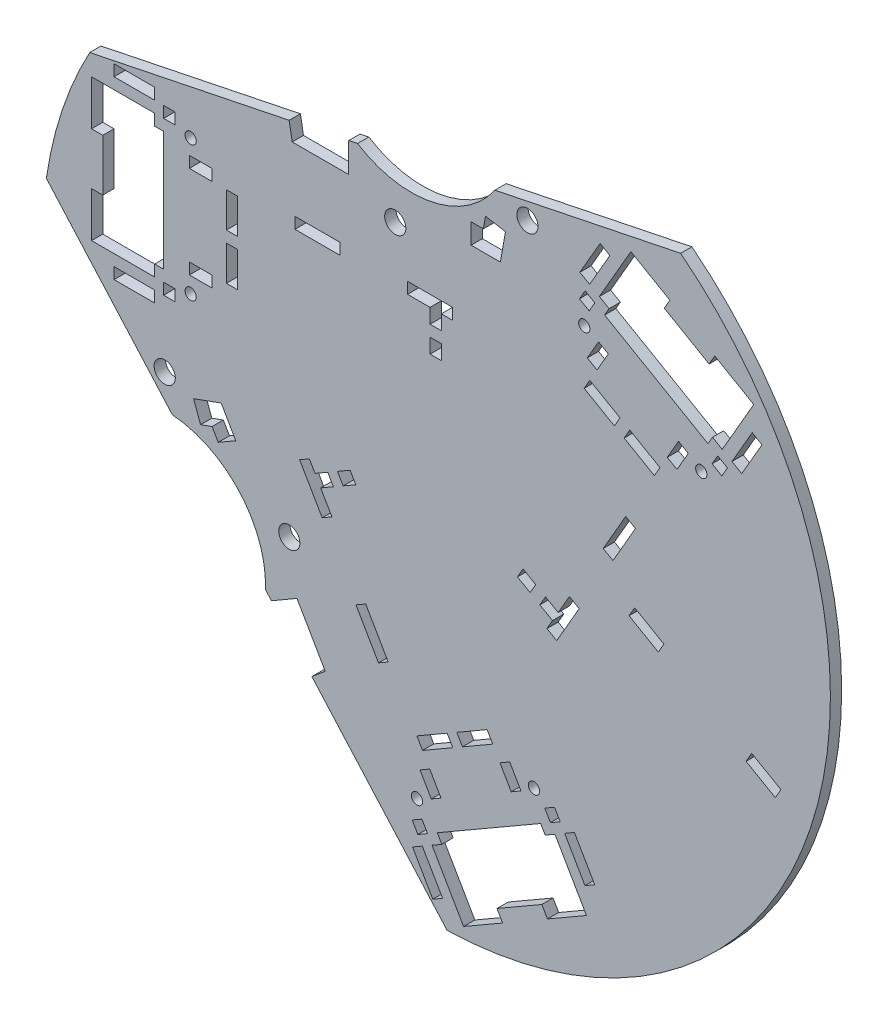
SolidWorks part; units mm, degrees
material "Balsa"
ref_plane "Plan de face" through (0, 0, 0) normal (0, 0, 1) x (1, 0, 0)
ref_plane "Plan de dessus" through (0, 0, 0) normal (0, 1, 0) x (1, 0, 0)
ref_plane "Plan de droite" through (0, 0, 0) normal (1, 0, 0) x (0, 0, -1)
sketch "Esquisse1" plane through (0, 0, 0) normal (0, 0, 1) x (1, 0, 0)
  circle A0 centre (148.0804, -12.1102) radius 175
extrude "Boss.-Extru.1" add sketch "Esquisse1" along normal blind 5
sketch "Esquisse2" plane through (0, 0, 0) normal (0, 0, -1) x (-1, 0, 0)
  line L0 (-155.3118, 53.7774) -> (-135.3118, 53.7774)
  line L1 (-150.3118, 37.2774) -> (-145.3118, 37.2774)
  line L2 (-150.3118, 37.2774) -> (-150.3118, 30.7774)
  line L3 (-150.3118, 30.7774) -> (-145.3118, 30.7774)
  line L4 (-145.3118, 37.2774) -> (-145.3118, 30.7774)
  line L5 (-105.3118, 53.7774) -> (-85.3118, 53.7774)
  line L6 (-105.3118, 53.7774) -> (-105.3118, 48.7774)
  line L7 (-105.3118, 48.7774) -> (-85.3118, 48.7774)
  line L8 (-85.3118, 53.7774) -> (-85.3118, 48.7774)
  line L9 (-59.86, 48.7774) -> (-54.86, 48.7774)
  line L10 (-59.86, 48.7774) -> (-59.86, 33.2774)
  line L11 (-59.86, 33.2774) -> (-54.86, 33.2774)
  line L12 (-54.86, 48.7774) -> (-54.86, 33.2774)
  line L13 (-59.86, 28.2774) -> (-54.86, 28.2774)
  line L14 (-59.86, 28.2774) -> (-59.86, 12.7774)
  line L15 (-59.86, 12.7774) -> (-54.86, 12.7774)
  line L16 (-54.86, 28.2774) -> (-54.86, 12.7774)
  line L17 (-48.43, 12.7774) -> (-38.43, 12.7774)
  line L18 (-48.43, 12.7774) -> (-48.43, 7.7774)
  line L19 (-48.43, 7.7774) -> (-38.43, 7.7774)
  line L20 (-38.43, 12.7774) -> (-38.43, 7.7774)
  line L21 (-32, -0.7226) -> (-27, -0.7226)
  line L22 (-32, -0.7226) -> (-32, -5.7226)
  line L23 (-32, -5.7226) -> (-27, -5.7226)
  line L24 (-27, -0.7226) -> (-27, -5.7226)
  line L25 (-23, -5.7226) -> (-5, -5.7226)
  line L26 (-23, -5.7226) -> (-23, -10.7226)
  line L27 (-23, -10.7226) -> (-5, -10.7226)
  line L28 (-5, -5.7226) -> (-5, -10.7226)
  line L29 (0, -0.7226) -> (5, -0.7226)
  line L30 (0, -0.7226) -> (0, 19.2774)
  line L31 (0, 19.2774) -> (5, 19.2774)
  line L32 (5, -0.7226) -> (5, 19.2774)
  line L33 (0, 42.2774) -> (5, 42.2774)
  line L34 (0, 42.2774) -> (0, 62.2774)
  line L35 (0, 62.2774) -> (5, 62.2774)
  line L36 (5, 42.2774) -> (5, 62.2774)
  line L37 (-23, 67.2774) -> (-5, 67.2774)
  line L38 (-23, 67.2774) -> (-23, 72.2774)
  line L39 (-23, 72.2774) -> (-5, 72.2774)
  line L40 (-5, 67.2774) -> (-5, 72.2774)
  line L41 (-27, 67.2774) -> (-32, 67.2774)
  line L42 (-27, 67.2774) -> (-27, 62.2774)
  line L43 (-27, 62.2774) -> (-32, 62.2774)
  line L44 (-32, 67.2774) -> (-32, 62.2774)
  line L45 (-38.43, 53.7774) -> (-48.43, 53.7774)
  line L46 (-38.43, 53.7774) -> (-38.43, 48.7774)
  line L47 (-38.43, 48.7774) -> (-48.43, 48.7774)
  line L48 (-48.43, 53.7774) -> (-48.43, 48.7774)
  line L49 (-135.3118, 53.7774) -> (-135.3118, 48.7774)
  line L50 (-135.3118, 48.7774) -> (-145.3118, 48.7774)
  line L51 (-135.3118, 48.7774) -> (-155.3118, 48.7774) construction
  line L52 (-145.3118, 48.7774) -> (-145.3118, 42.2774)
  line L53 (-145.3118, 42.2774) -> (-150.3118, 42.2774)
  line L54 (-150.3118, 42.2774) -> (-150.3118, 48.7774)
  line L55 (-150.3118, 48.7774) -> (-155.3118, 48.7774)
  line L56 (-155.3118, 48.7774) -> (-155.3118, 53.7774)
  line L57 (-87.4044, -38.7914) -> (-97.4044, -56.1119)
  line L58 (-104.1938, -34.8716) -> (-106.6938, -39.2017)
  line L59 (-104.1938, -34.8716) -> (-109.823, -31.6216)
  line L60 (-109.823, -31.6216) -> (-112.323, -35.9517)
  line L61 (-106.6938, -39.2017) -> (-112.323, -35.9517)
  line L62 (-112.4044, -82.0927) -> (-122.4044, -99.4132)
  line L63 (-112.4044, -82.0927) -> (-116.7345, -79.5927)
  line L64 (-116.7345, -79.5927) -> (-126.7345, -96.9132)
  line L65 (-122.4044, -99.4132) -> (-126.7345, -96.9132)
  line L66 (-139.4604, -118.9551) -> (-141.9604, -123.2852)
  line L67 (-139.4604, -118.9551) -> (-152.8838, -111.2051)
  line L68 (-152.8838, -111.2051) -> (-155.3838, -115.5352)
  line L69 (-141.9604, -123.2852) -> (-155.3838, -115.5352)
  line L70 (-157.2139, -108.7051) -> (-159.7139, -113.0352)
  line L71 (-157.2139, -108.7051) -> (-170.6373, -100.9551)
  line L72 (-170.6373, -100.9551) -> (-173.1373, -105.2852)
  line L73 (-159.7139, -113.0352) -> (-173.1373, -105.2852)
  line L74 (-176.3523, -110.8538) -> (-181.3523, -119.514)
  line L75 (-176.3523, -110.8538) -> (-180.6825, -108.3538)
  line L76 (-180.6825, -108.3538) -> (-185.6825, -117.014)
  line L77 (-181.3523, -119.514) -> (-185.6825, -117.014)
  line L78 (-196.2587, -118.3326) -> (-198.7587, -122.6627)
  line L79 (-196.2587, -118.3326) -> (-200.5888, -115.8326)
  line L80 (-200.5888, -115.8326) -> (-203.0888, -120.1627)
  line L81 (-198.7587, -122.6627) -> (-203.0888, -120.1627)
  line L82 (-205.0888, -123.6268) -> (-214.0888, -139.2153)
  line L83 (-205.0888, -123.6268) -> (-209.4189, -121.1268)
  line L84 (-209.4189, -121.1268) -> (-218.4189, -136.7153)
  line L85 (-214.0888, -139.2153) -> (-218.4189, -136.7153)
  line L86 (-212.2587, -146.0454) -> (-214.7587, -150.3755)
  line L87 (-212.2587, -146.0454) -> (-194.9382, -156.0454)
  line L88 (-194.9382, -156.0454) -> (-197.4382, -160.3755)
  line L89 (-214.7587, -150.3755) -> (-197.4382, -160.3755)
  line L90 (-175.0196, -167.5454) -> (-177.5196, -171.8755)
  line L91 (-175.0196, -167.5454) -> (-157.6991, -177.5454)
  line L92 (-157.6991, -177.5454) -> (-160.1991, -181.8755)
  line L93 (-177.5196, -171.8755) -> (-160.1991, -181.8755)
  line L94 (-141.869, -160.1268) -> (-150.869, -175.7153)
  line L95 (-141.869, -160.1268) -> (-137.5388, -162.6268)
  line L96 (-137.5388, -162.6268) -> (-146.5388, -178.2153)
  line L97 (-150.869, -175.7153) -> (-146.5388, -178.2153)
  line L98 (-139.869, -156.6627) -> (-137.369, -152.3326)
  line L99 (-139.869, -156.6627) -> (-144.1991, -154.1627)
  line L100 (-144.1991, -154.1627) -> (-141.6991, -149.8326)
  line L101 (-137.369, -152.3326) -> (-141.6991, -149.8326)
  line L102 (-145.8453, -140.014) -> (-140.8453, -131.3538)
  line L103 (-145.8453, -140.014) -> (-150.1754, -137.514)
  line L104 (-150.1754, -137.514) -> (-145.1754, -128.8538)
  line L105 (-140.8453, -131.3538) -> (-145.1754, -128.8538)
  line L106 (-97.4044, -56.1119) -> (-101.7345, -53.6119)
  line L107 (-101.7345, -53.6119) -> (-96.7345, -44.9517)
  line L108 (-96.7345, -44.9517) -> (-102.3637, -41.7017)
  line L109 (-102.3637, -41.7017) -> (-99.8637, -37.3716)
  line L110 (-99.8637, -37.3716) -> (-94.2345, -40.6216)
  line L111 (-94.2345, -40.6216) -> (-91.7345, -36.2914)
  line L112 (-91.7345, -36.2914) -> (-87.4044, -38.7914)
  line L113 (-201.5251, -51.3165) -> (-211.5251, -33.996)
  line L114 (-189.7357, -38.7364) -> (-192.2357, -34.4063)
  line L115 (-189.7357, -38.7364) -> (-184.1065, -35.4864)
  line L116 (-184.1065, -35.4864) -> (-186.6065, -31.1563)
  line L117 (-192.2357, -34.4063) -> (-186.6065, -31.1563)
  line L118 (-226.5251, -8.0153) -> (-236.5251, 9.3053)
  line L119 (-226.5251, -8.0153) -> (-222.195, -5.5153)
  line L120 (-222.195, -5.5153) -> (-232.195, 11.8053)
  line L121 (-236.5251, 9.3053) -> (-232.195, 11.8053)
  line L122 (-244.9209, 33.8472) -> (-247.4209, 38.1773)
  line L123 (-244.9209, 33.8472) -> (-231.4975, 41.5972)
  line L124 (-231.4975, 41.5972) -> (-233.9975, 45.9273)
  line L125 (-247.4209, 38.1773) -> (-233.9975, 45.9273)
  line L126 (-227.1673, 44.0972) -> (-229.6673, 48.4273)
  line L127 (-227.1673, 44.0972) -> (-213.7439, 51.8472)
  line L128 (-213.7439, 51.8472) -> (-216.2439, 56.1773)
  line L129 (-229.6673, 48.4273) -> (-216.2439, 56.1773)
  line L130 (-219.4589, 61.7458) -> (-224.4589, 70.4061)
  line L131 (-219.4589, 61.7458) -> (-215.1288, 64.2458)
  line L132 (-215.1288, 64.2458) -> (-220.1288, 72.9061)
  line L133 (-224.4589, 70.4061) -> (-220.1288, 72.9061)
  line L134 (-215.9826, 82.7246) -> (-218.4826, 87.0547)
  line L135 (-215.9826, 82.7246) -> (-211.6525, 85.2246)
  line L136 (-211.6525, 85.2246) -> (-214.1525, 89.5547)
  line L137 (-218.4826, 87.0547) -> (-214.1525, 89.5547)
  line L138 (-216.1525, 93.0188) -> (-225.1525, 108.6073)
  line L139 (-216.1525, 93.0188) -> (-211.8223, 95.5188)
  line L140 (-211.8223, 95.5188) -> (-220.8223, 111.1073)
  line L141 (-225.1525, 108.6073) -> (-220.8223, 111.1073)
  line L142 (-231.9826, 110.4374) -> (-234.4826, 114.7676)
  line L143 (-231.9826, 110.4374) -> (-249.3031, 100.4374)
  line L144 (-249.3031, 100.4374) -> (-251.8031, 104.7676)
  line L145 (-234.4826, 114.7676) -> (-251.8031, 104.7676)
  line L146 (-269.2217, 88.9374) -> (-271.7217, 93.2676)
  line L147 (-269.2217, 88.9374) -> (-286.5422, 78.9374)
  line L148 (-286.5422, 78.9374) -> (-289.0422, 83.2676)
  line L149 (-271.7217, 93.2676) -> (-289.0422, 83.2676)
  line L150 (-279.3723, 56.5188) -> (-288.3723, 72.1073)
  line L151 (-279.3723, 56.5188) -> (-283.7025, 54.0188)
  line L152 (-283.7025, 54.0188) -> (-292.7025, 69.6073)
  line L153 (-288.3723, 72.1073) -> (-292.7025, 69.6073)
  line L154 (-277.3723, 53.0547) -> (-274.8723, 48.7246)
  line L155 (-277.3723, 53.0547) -> (-273.0422, 55.5547)
  line L156 (-273.0422, 55.5547) -> (-270.5422, 51.2246)
  line L157 (-274.8723, 48.7246) -> (-270.5422, 51.2246)
  line L158 (-259.966, 49.9061) -> (-254.966, 41.2458)
  line L159 (-259.966, 49.9061) -> (-255.6359, 52.4061)
  line L160 (-255.6359, 52.4061) -> (-250.6359, 43.7458)
  line L161 (-254.966, 41.2458) -> (-250.6359, 43.7458)
  line L162 (-211.5251, -33.996) -> (-207.195, -31.496)
  line L163 (-207.195, -31.496) -> (-202.195, -40.1563)
  line L164 (-202.195, -40.1563) -> (-196.5658, -36.9063)
  line L165 (-196.5658, -36.9063) -> (-194.0658, -41.2364)
  line L166 (-194.0658, -41.2364) -> (-199.695, -44.4864)
  line L167 (-199.695, -44.4864) -> (-197.195, -48.8165)
  line L168 (-197.195, -48.8165) -> (-201.5251, -51.3165)
  point P204 (-148.0804, -12.1102)
  dimension "D1" = 3
extrude "Enlèv. mat.-Extru.1" cut sketch "Esquisse2" against normal blind 5
sketch "Esquisse3" plane through (0, 0, 0) normal (0, 0, -1) x (-1, 0, 0)
  line L0 (-59.86, 33.2774) -> (-59.86, 28.2774) construction
  line L1 (-59.86, 30.7774) -> (32.4397, 30.7774) construction
  line L2 (0, -0.7226) -> (-23, -0.7226)
  line L3 (-23, -0.7226) -> (-23, 4.2774)
  line L4 (-23, 4.2774) -> (-27, 4.2774)
  line L5 (-23, 57.2774) -> (-27, 57.2774)
  line L6 (-23, 62.2774) -> (-23, 57.2774)
  line L7 (0, 62.2774) -> (-23, 62.2774)
  line L8 (-27, 57.2774) -> (-27, 4.2774)
  line L9 (0, -0.7226) -> (0, 62.2774)
  line L10 (-212.2587, -146.0454) -> (-200.7587, -126.1268)
  line L11 (-200.7587, -126.1268) -> (-196.4286, -128.6268)
  line L12 (-196.4286, -128.6268) -> (-194.4286, -125.1627)
  line L13 (-150.5292, -155.1268) -> (-148.5292, -151.6627)
  line L14 (-146.1991, -157.6268) -> (-150.5292, -155.1268)
  line L15 (-157.6991, -177.5454) -> (-146.1991, -157.6268)
  line L16 (-148.5292, -151.6627) -> (-194.4286, -125.1627)
  line L17 (-212.2587, -146.0454) -> (-157.6991, -177.5454)
  line L18 (-152.8838, -111.2051) -> (-157.2139, -108.7051) construction
  line L19 (-155.0489, -109.9551) -> (-201.1987, -189.889) construction
  line L20 (-231.9826, 110.4374) -> (-220.4826, 90.5188)
  line L21 (-220.4826, 90.5188) -> (-224.8127, 88.0188)
  line L22 (-224.8127, 88.0188) -> (-222.8127, 84.5547)
  line L23 (-270.7121, 61.5188) -> (-268.7121, 58.0547)
  line L24 (-275.0422, 59.0188) -> (-270.7121, 61.5188)
  line L25 (-286.5422, 78.9374) -> (-275.0422, 59.0188)
  line L26 (-268.7121, 58.0547) -> (-222.8127, 84.5547)
  line L27 (-231.9826, 110.4374) -> (-286.5422, 78.9374)
  line L28 (-231.4975, 41.5972) -> (-227.1673, 44.0972) construction
  line L29 (-229.3324, 42.8472) -> (-275.4822, 122.781) construction
  point P42 (-148.0804, -12.1102)
  dimension "D1" = 5
  dimension "D2" = 4
  dimension "D3" = 23
  dimension "D4" = 3
extrude "Enlèv. mat.-Extru.2" cut sketch "Esquisse3" against normal blind 5
sketch "Esquisse4" plane through (0, 0, 0) normal (0, 0, -1) x (-1, 0, 0)
  line L0 (-32, 67.2774) -> (-32, 62.2774) construction
  line L1 (-38.43, 53.7774) -> (-48.43, 53.7774) construction
  line L2 (-27, 30.7774) -> (-93.5454, 30.7774) construction
  line L3 (-27, 57.2774) -> (-27, 4.2774) construction
  line L4 (-171.4789, -138.4127) -> (-138.2062, -80.7827) construction
  line L5 (-245.7624, 71.3047) -> (-212.4897, 13.6748) construction
  circle A0 centre (-39, 60.7774) radius 2.5
  circle A1 centre (-39, 0.7774) radius 2.5
  circle A2 centre (-139.4981, -143.0204) radius 2.5
  circle A3 centre (-191.4596, -113.0204) radius 2.5
  circle A4 centre (-265.7432, 45.9124) radius 2.5
  circle A5 centre (-213.7816, 75.9124) radius 2.5
  point P27 (-148.0804, -12.1102)
  dimension "D1" = 7
  dimension "D2" = 7
  dimension "D3" = 3
extrude "Enlèv. mat.-Extru.3" cut sketch "Esquisse4" against normal blind 5
sketch "Esquisse5" plane through (0, 0, 0) normal (0, 0, -1) x (-1, 0, 0)
  line L0 (9.513, 70.4436) -> (-93.4749, 91.6327)
  line L1 (-315.6991, 137.3538) -> (-290.787, 258.4375)
  line L2 (-290.787, 258.4375) -> (34.4251, 191.5273)
  line L3 (34.4251, 191.5273) -> (9.513, 70.4436)
  line L4 (-233.6714, -25.6375) -> (-246.6617, -33.1375)
  line L5 (-179.3609, 109.3031) -> (-315.6991, 137.3538)
  line L6 (-94.86, 83.7774) -> (-174.86, 83.7774)
  line L7 (-174.86, 83.7774) -> (-179.3609, 109.3031)
  line L8 (-233.6714, -25.6375) -> (-236.1714, -21.3074)
  line L9 (-93.4749, 91.6327) -> (-94.86, 83.7774)
  line L10 (-155.3834, -189.8669) -> (-85.5392, -111.2714)
  line L11 (65.1685, 58.3199) -> (157.574, -23.7965)
  line L12 (26.9196, -12.1102) -> (-148.0804, -12.1102) construction
  line L13 (157.574, -23.7965) -> (-62.9779, -271.9834)
  line L14 (-62.9779, -271.9834) -> (-155.3834, -189.8669)
  line L15 (-246.6617, -33.1375) -> (-249.1617, -28.8074)
  line L16 (-27.2932, -45.7272) -> (65.1685, 58.3199)
  line L17 (-91.6495, -106.1442) -> (-51.6495, -36.8622)
  line L18 (-51.6495, -36.8622) -> (-27.2932, -45.7272)
  line L19 (-236.1714, -21.3074) -> (-249.1617, -28.8074)
  line L20 (-85.5392, -111.2714) -> (-91.6495, -106.1442)
  line L21 (-148.0804, -12.1102) -> (-235.5804, -163.6646) construction
  line L22 (-93.4749, 91.6327) -> (-179.3609, 109.3031) construction
  line L23 (-139.86, 83.7774) -> (-139.86, 101.1761) construction
  line L24 (-285.6329, -55.6375) -> (-298.6233, -63.1375)
  line L25 (-285.6329, -55.6375) -> (-288.1329, -51.3074)
  line L26 (-298.6233, -63.1375) -> (-301.1233, -58.8074)
  line L27 (-288.1329, -51.3074) -> (-301.1233, -58.8074)
  line L28 (-211.5251, -33.996) -> (-201.5251, -51.3165) construction
  line L29 (-283.7025, 54.0188) -> (-279.3723, 56.5188) construction
  circle A0 centre (-188.5408, 103.7774) radius 4.7
  circle A1 centre (-129.86, 73.7774) radius 4.7
  circle A2 centre (-27.4886, -35.0143) radius 4.7
  circle A3 centre (-82.8098, -70.8333) radius 4.7
  point P15 (-148.0804, -12.1102)
  point P35 (-148.0804, -12.1102)
  dimension "D2" = 9.4
  dimension "D3" = 9.4
  dimension "D4" = 100
  dimension "D5" = 100
  dimension "D6" = 5
  dimension "D7" = 45
  dimension "D8" = 15
  dimension "D9" = 80
  dimension "D10" = 35
  dimension "D11" = 85.8876
  dimension "D12" = 58.6808
  dimension "D13" = 30
  dimension "D14" = 10
  dimension "D15" = 11.626
  dimension "D16" = 18.2204
  dimension "D18" = 17.3986
  dimension "D19" = 15
  dimension "D20" = 45
  dimension "D21" = 15
  dimension "D22" = 89
  dimension "D17" = 2
extrude "Enlèv. mat.-Extru.4" cut sketch "Esquisse5" against normal blind 5
sketch "Esquisse6" plane through (0, 0, 0) normal (0, 0, -1) x (-1, 0, 0)
  line L7 (-72.2193, -96.2825) -> (-85.5392, -111.2714)
  line L8 (-85.5392, -111.2714) -> (-94.4781, -107.3647)
  line L9 (-94.4781, -107.3647) -> (-52.0208, -31.4132)
  line L10 (-52.0208, -31.4132) -> (-27.2932, -45.7272)
  line L11 (-27.2932, -45.7272) -> (-30.866, -49.7477)
  line L13 (-113.1156, 95.6736) -> (-93.4749, 91.6327)
  line L14 (-93.4749, 91.6327) -> (-92.3887, 81.938)
  line L15 (-92.3887, 81.938) -> (-179.3934, 80.7314)
  line L16 (-179.3934, 80.7314) -> (-179.3609, 109.3031)
  line L17 (-179.3609, 109.3031) -> (-174.0926, 108.2192)
  arc A0 (-72.2193, -96.2825) -> (-30.866, -49.7477) centre (-27.2507, -94.6022) cw
  arc A2 (-113.1156, 95.6736) -> (-174.0926, 108.2192) centre (-137.0551, 133.7774) cw
  point P3 (-148.0804, -12.1102)
  point P21 (-148.0804, -12.1102)
  dimension "D1" = 45
  dimension "D2" = 2
extrude "Boss.-Extru.2" add sketch "Esquisse6" against normal blind 5
sketch "Esquisse7" plane through (0, 0, 0) normal (0, 0, -1) x (-1, 0, 0)
  line L0 (-109.1977, 94.8675) -> (-109.1977, 81.7774)
  line L1 (-113.1156, 95.6736) -> (5.8145, 71.2045) construction
  line L2 (-109.1977, 81.7774) -> (-84.1003, 81.7774)
  line L3 (-84.1003, 81.7774) -> (-82.7516, 89.4264)
  line L4 (-82.7516, 89.4264) -> (-109.1977, 94.8675)
  line L5 (26.9196, -12.1102) -> (-148.0804, -12.1102) construction
  line L6 (-74.8764, -99.2725) -> (-86.2127, -92.7274)
  line L7 (-163.5382, 81.7774) -> (-176.5382, 81.7774)
  line L8 (-176.5382, 81.7774) -> (-178.7956, 94.5799)
  line L9 (-178.7956, 94.5799) -> (-169.9324, 96.1428)
  line L10 (-169.9324, 96.1428) -> (-168.9863, 90.7774)
  line L12 (-168.9863, 90.7774) -> (-163.5382, 90.7774)
  line L13 (-163.5382, 90.7774) -> (-163.5382, 81.7774)
  line L14 (-86.2127, -92.7274) -> (-98.7614, -114.4624)
  line L15 (-98.7614, -114.4624) -> (-92.8116, -119.4549)
  line L16 (-92.8116, -119.4549) -> (-74.8764, -99.2725)
  line L17 (-59.0425, -45.6672) -> (-52.5425, -34.4088)
  line L18 (-52.5425, -34.4088) -> (-40.3265, -38.8551)
  line L19 (-40.3265, -38.8551) -> (-43.4047, -47.3123)
  line L20 (-43.4047, -47.3123) -> (-48.5242, -45.449)
  line L21 (-48.5242, -45.449) -> (-51.2483, -50.1672)
  line L22 (-51.2483, -50.1672) -> (-59.0425, -45.6672)
  point P14 (-148.0804, -12.1102)
  point P31 (-148.0804, -12.1102)
  dimension "D1" = 80
  dimension "D2" = 13.0901
  dimension "D3" = 4
  dimension "D4" = 27
  dimension "D5" = 20
  dimension "D6" = 9
  dimension "D7" = 9
  dimension "D8" = 7
  dimension "D9" = 13
  dimension "D10" = 13
  dimension "D11" = 2
extrude "Enlèv. mat.-Extru.5" cut sketch "Esquisse7" against normal blind 5
